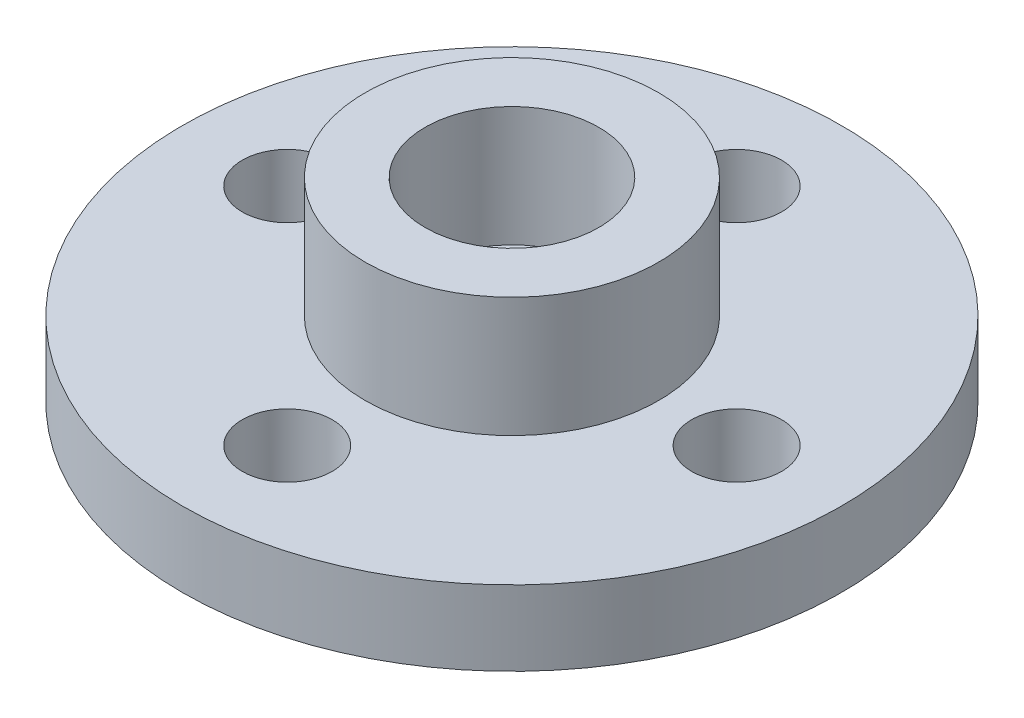
SolidWorks part; units mm, degrees
ref_plane "Front Plane" through (0, 0, 0) normal (0, 0, 1) x (1, 0, 0)
ref_plane "Top Plane" through (0, 0, 0) normal (0, 1, 0) x (1, 0, 0)
ref_plane "Right Plane" through (0, 0, 0) normal (1, 0, 0) x (0, 0, -1)
sketch "Sketch1" plane through (0, 0, 0) normal (0, 1, 0) x (1, 0, 0)
  circle A0 centre (0, 0) radius 11
  dimension "D1" = 22
extrude "Boss-Extrude1" add sketch "Sketch1" along normal blind 2.5
sketch "Sketch2" plane through (0, 2.5, 0) normal (0, 1, 0) x (1, 0, 0)
  line L0 (0, 0) -> (11, 0) construction
  line L1 (0, 0) -> (0, 11) construction
  line L2 (0, 0) -> (7.7782, 7.7782) construction
  line L3 (0, 0) -> (7.7782, -7.7782) construction
  circle A0 centre (0, 0) radius 11 construction
  circle A1 centre (7.5, 0) radius 1.5
  circle A2 centre (0, 0) radius 1.5
  circle A3 centre (0, 7.5) radius 1.5
  circle A4 centre (-7.5, 0) radius 1.5
  circle A5 centre (0, -7.5) radius 1.5
  dimension "D1" = 3
  dimension "D2" = 7.5
extrude "Cut-Extrude1" cut sketch "Sketch2" against normal blind 3
sketch "Sketch3" plane through (0, 2.5, 0) normal (0, 1, 0) x (1, 0, 0)
  circle A0 centre (0, 0) radius 2.9
  circle A1 centre (0, 0) radius 4.9
  dimension "D1" = 5.8
  dimension "D2" = 2
extrude "Boss-Extrude2" add sketch "Sketch3" along normal blind 4 contours A1 | A0
